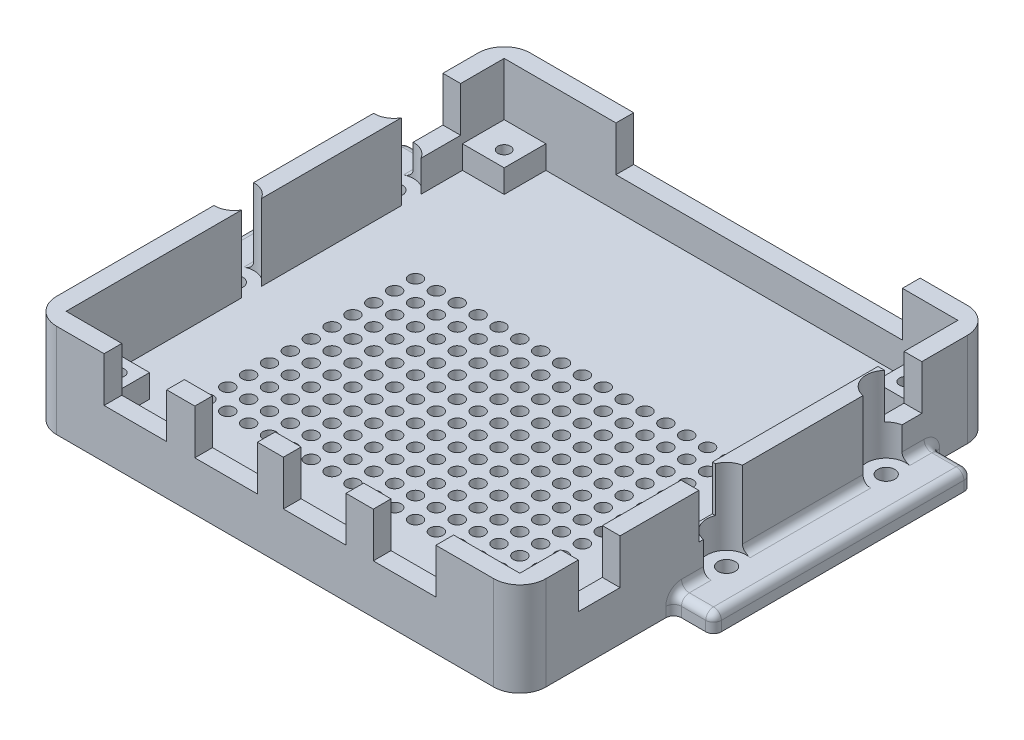
SolidWorks part; units mm, degrees
material "ABS"
ref_plane "Front Plane" through (0, 0, 0) normal (0, 0, 1) x (1, 0, 0)
ref_plane "Top Plane" through (0, 0, 0) normal (0, 1, 0) x (1, 0, 0)
ref_plane "Right Plane" through (0, 0, 0) normal (1, 0, 0) x (0, 0, -1)
sketch "Sketch1" plane through (0, 60.3244, 0) normal (0, 1, 0) x (1, 0, 0)
  line L0 (-17.8987, -37.9421) -> (-17.8987, -46.2606) construction
  line L1 (-17.8987, -46.2606) -> (-17.8987, -58.5796) construction
  line L2 (-24.7567, -58.5796) -> (-11.0407, -58.5796) construction
  line L3 (-17.8987, -58.5796) -> (-17.8987, -139.5421) construction
  line L4 (-17.8987, -139.5421) -> (-6.8751, -139.5421) construction
  line L5 (-17.8987, -139.5421) -> (87.5113, -139.5421) construction
  line L6 (-6.8751, -139.5421) -> (8.3649, -139.5421) construction
  line L7 (8.3649, -139.5421) -> (15.2229, -139.5421) construction
  line L8 (15.2229, -139.5421) -> (30.4629, -139.5421) construction
  line L9 (30.4629, -139.5421) -> (36.7875, -139.5421) construction
  line L10 (36.7875, -139.5421) -> (52.0275, -139.5421) construction
  line L11 (52.0275, -139.5421) -> (58.6823, -139.5421) construction
  line L12 (58.6823, -139.5421) -> (73.9223, -139.5421) construction
  line L13 (73.9223, -139.5421) -> (87.5113, -139.5421) construction
  line L14 (87.5113, -139.5421) -> (87.5113, -132.1507) construction
  line L15 (87.5113, -102.8137) -> (87.5113, -139.5421) construction
  line L16 (87.5113, -132.1507) -> (87.5113, -121.9907) construction
  line L17 (87.5113, -121.9907) -> (87.5113, -102.8137) construction
  line L18 (87.5113, -102.8137) -> (87.5113, -95.1937) construction
  line L19 (87.5113, -95.1937) -> (87.5113, -54.8585) construction
  line L20 (87.5113, -37.9421) -> (87.5113, -95.1937) construction
  line L21 (87.5113, -54.8585) -> (87.5113, -48.5085) construction
  line L22 (87.5113, -48.5085) -> (87.5113, -37.9421) construction
  line L23 (87.5113, -37.9421) -> (76.5401, -37.9421) construction
  line L24 (-17.8987, -37.9421) -> (87.5113, -37.9421) construction
  line L25 (76.5401, -37.9421) -> (53.8801, -37.9421) construction
  line L26 (53.8801, -37.9421) -> (52.3339, -37.9421) construction
  line L27 (52.3339, -37.9421) -> (29.6739, -37.9421) construction
  line L28 (29.6739, -37.9421) -> (29.4485, -37.9421) construction
  line L29 (29.4485, -37.9421) -> (6.7885, -37.9421) construction
  line L30 (6.7885, -37.9421) -> (-17.8987, -37.9421) construction
  line L31 (-24.7567, -58.712) -> (-24.7567, -146.4001)
  line L32 (-20.4387, -142.0821) -> (-6.8751, -142.0821)
  line L33 (6.7885, -35.4021) -> (-20.4387, -35.4021)
  line L34 (-24.7567, -31.0841) -> (-24.7567, -46.0066)
  line L35 (90.0513, -48.5085) -> (90.0513, -35.4021)
  line L36 (90.0513, -35.4021) -> (76.5401, -35.4021)
  line L37 (90.0513, -95.1937) -> (90.0513, -54.8585)
  line L38 (90.0513, -121.9907) -> (90.0513, -102.8137)
  line L39 (73.9223, -142.0821) -> (90.0513, -142.0821)
  line L40 (90.0513, -142.0821) -> (90.0513, -132.1507)
  line L41 (52.0275, -142.0821) -> (58.6823, -142.0821)
  line L42 (30.4629, -142.0821) -> (36.7875, -142.0821)
  line L43 (8.3649, -142.0821) -> (15.2229, -142.0821)
  line L44 (6.7885, -31.0841) -> (-24.7567, -31.0841)
  line L45 (-20.4387, -46.0066) -> (-20.4387, -35.4021)
  line L46 (-20.4387, -142.0821) -> (-20.4387, -58.712)
  line L47 (-24.7567, -146.4001) -> (-6.8751, -146.4001)
  line L48 (8.3649, -146.4001) -> (15.2229, -146.4001)
  line L49 (30.4629, -146.4001) -> (36.7875, -146.4001)
  line L50 (52.0275, -146.4001) -> (58.6823, -146.4001)
  line L51 (73.9223, -146.4001) -> (94.3693, -146.4001)
  line L52 (94.3693, -146.4001) -> (94.3693, -132.1507)
  line L53 (94.3693, -121.9907) -> (94.3693, -102.8137)
  line L54 (94.3693, -95.1937) -> (94.3693, -54.8585)
  line L55 (94.3693, -48.5085) -> (94.3693, -31.0841)
  line L56 (94.3693, -31.0841) -> (76.5401, -31.0841)
  line L57 (-24.7567, -58.712) -> (-20.4387, -58.712)
  line L58 (-24.7567, -46.0066) -> (-20.4387, -46.0066)
  line L60 (-24.7567, -58.5796) -> (-17.8987, -58.5796) construction
  line L62 (6.7885, -31.0841) -> (6.7885, -35.4021)
  line L63 (76.5401, -35.4021) -> (76.5401, -31.0841)
  line L64 (90.0513, -48.5085) -> (94.3693, -48.5085)
  line L65 (90.0513, -54.8585) -> (94.3693, -54.8585)
  line L66 (90.0513, -95.1937) -> (94.3693, -95.1937)
  line L67 (90.0513, -102.8137) -> (94.3693, -102.8137)
  line L68 (90.0513, -121.9907) -> (94.3693, -121.9907)
  line L69 (90.0513, -132.1507) -> (94.3693, -132.1507)
  line L70 (73.9223, -142.0821) -> (73.9223, -146.4001)
  line L71 (58.6823, -146.4001) -> (58.6823, -142.0821)
  line L72 (52.0275, -142.0821) -> (52.0275, -146.4001)
  line L73 (36.7875, -146.4001) -> (36.7875, -142.0821)
  line L74 (30.4629, -142.0821) -> (30.4629, -146.4001)
  line L75 (15.2229, -142.0821) -> (15.2229, -146.4001)
  line L76 (8.3649, -142.0821) -> (8.3649, -146.4001)
  line L77 (-6.8751, -142.0821) -> (-6.8751, -146.4001)
  line L78 (-24.7567, -58.5796) -> (-24.7567, -146.4001) construction
  line L79 (-20.4387, -58.5796) -> (-20.4387, -142.0821) construction
  line L80 (-24.7567, -31.0841) -> (-24.7567, -46.2606) construction
  line L81 (-20.4387, -35.4021) -> (-20.4387, -46.2606) construction
  dimension "D1" = 0.1324
extrude "Boss-Extrude2" add sketch "Sketch1" along normal up to surface (10.922 mm away)
sketch "Sketch2" plane through (0, 60.3244, 0) normal (0, -1, 0) x (1, 0, 0)
  line L0 (87.5113, 37.9421) -> (87.5113, 139.5421) construction
  line L1 (-24.7567, 146.4001) -> (94.3693, 146.4001)
  line L2 (-24.7567, 146.4001) -> (-24.7567, 31.0841)
  line L3 (-24.7567, 31.0841) -> (94.3693, 31.0841)
  line L4 (94.3693, 146.4001) -> (94.3693, 31.0841)
  line L5 (-10.2787, 45.5621) -> (-17.8987, 45.5621)
  line L6 (-10.2787, 45.5621) -> (-10.2787, 37.9421)
  line L7 (-10.2787, 37.9421) -> (-17.8987, 37.9421)
  line L8 (-17.8987, 45.5621) -> (-17.8987, 37.9421)
  line L9 (-10.2787, 45.5621) -> (-17.8987, 37.9421) construction
  line L10 (-10.2787, 37.9421) -> (-17.8987, 45.5621) construction
  line L11 (-10.2787, 131.9221) -> (-17.8987, 131.9221)
  line L12 (-10.2787, 131.9221) -> (-10.2787, 139.5421)
  line L13 (-10.2787, 139.5421) -> (-17.8987, 139.5421)
  line L14 (-17.8987, 131.9221) -> (-17.8987, 139.5421)
  line L15 (-10.2787, 131.9221) -> (-17.8987, 139.5421) construction
  line L16 (-10.2787, 139.5421) -> (-17.8987, 131.9221) construction
  line L17 (79.8913, 131.9221) -> (87.5113, 131.9221)
  line L18 (79.8913, 131.9221) -> (79.8913, 139.5421)
  line L19 (79.8913, 139.5421) -> (87.5113, 139.5421)
  line L20 (87.5113, 131.9221) -> (87.5113, 139.5421)
  line L21 (79.8913, 131.9221) -> (87.5113, 139.5421) construction
  line L22 (79.8913, 139.5421) -> (87.5113, 131.9221) construction
  line L23 (79.8913, 45.5621) -> (87.5113, 45.5621)
  line L24 (79.8913, 45.5621) -> (79.8913, 37.9421)
  line L25 (79.8913, 37.9421) -> (87.5113, 37.9421)
  line L26 (87.5113, 45.5621) -> (87.5113, 37.9421)
  line L27 (79.8913, 45.5621) -> (87.5113, 37.9421) construction
  line L28 (79.8913, 37.9421) -> (87.5113, 45.5621) construction
  line L29 (-17.8987, 37.9421) -> (87.5113, 37.9421) construction
  line L30 (-24.7567, 46.0066) -> (-20.4387, 46.0066)
  line L31 (-10.2787, 131.9221) -> (-24.7567, 131.9221)
  line L32 (-10.2787, 131.9221) -> (-10.2787, 146.4001)
  line L33 (-10.2787, 146.4001) -> (-24.7567, 146.4001)
  line L34 (-24.7567, 131.9221) -> (-24.7567, 146.4001)
  line L35 (79.8913, 131.9221) -> (94.3693, 131.9221)
  line L36 (79.8913, 131.9221) -> (79.8913, 146.4001)
  line L37 (79.8913, 146.4001) -> (94.3693, 146.4001)
  line L38 (94.3693, 131.9221) -> (94.3693, 146.4001)
  line L39 (-10.2787, 45.5621) -> (-24.7567, 45.5621)
  line L40 (-10.2787, 45.5621) -> (-10.2787, 31.0841)
  line L41 (-10.2787, 31.0841) -> (-24.7567, 31.0841)
  line L42 (-24.7567, 45.5621) -> (-24.7567, 31.0841)
  line L43 (79.8913, 45.5621) -> (94.3693, 45.5621)
  line L44 (79.8913, 45.5621) -> (79.8913, 31.0841)
  line L45 (79.8913, 31.0841) -> (94.3693, 31.0841)
  line L46 (94.3693, 45.5621) -> (94.3693, 31.0841)
  line L47 (-20.4387, 46.0066) -> (-20.4387, 45.5621)
  line L48 (-20.4387, 46.0066) -> (-20.4387, 35.4021) construction
  line L49 (-20.4387, 45.5621) -> (-24.7567, 45.5621)
  line L51 (-20.4387, 142.0821) -> (90.0513, 142.0821)
  line L52 (-20.4387, 142.0821) -> (-20.4387, 35.4021)
  line L53 (-20.4387, 35.4021) -> (90.0513, 35.4021)
  line L54 (90.0513, 142.0821) -> (90.0513, 35.4021)
  circle A0 centre (83.7013, 135.7321) radius 1.524
  circle A1 centre (-14.0887, 135.7321) radius 1.524
  circle A2 centre (-14.0887, 41.7521) radius 1.524
  circle A3 centre (83.7013, 41.7521) radius 1.524
  point P6 (-14.0887, 41.7521)
  point P13 (-14.0887, 135.7321)
  point P20 (83.7013, 135.7321)
  point P27 (83.7013, 41.7521)
  line M1 (-20.4387, 58.712) -> (-20.4387, 142.0821)
  line M2 (-20.4387, 142.0821) -> (-6.8751, 142.0821)
  line M3 (-6.8751, 142.0821) -> (-6.8751, 146.4001)
  line M4 (-6.8751, 146.4001) -> (-24.7567, 146.4001)
  line M5 (-24.7567, 146.4001) -> (-24.7567, 58.712)
  line M6 (-24.7567, 58.712) -> (-20.4387, 58.712)
extrude "Boss-Extrude4" add sketch "Sketch2" along normal blind 7.62 contours L43 L54 L53 L44 L3 L4 | L35 L54 L43 L4 | L51 L54 L35 L4 L1 L36 | L53 L40 L3 L44 | L53 L52 L39 L2 L3 L40 | L52 L2 L30 M6 | L47 L30 L2 L39 | L31 L2 M1 M6 | L32 L1 L31 M2 M5 M1 | L32 M2 M3 M4 | L51 L36 L1 M3 region at (-17.5177, 60.3244, 146.1953) region at (-8.5769, 60.3244, 144.2411) region at (-22.5977, 60.3244, 95.317) region at (36.5081, 60.3244, 144.2411) region at (-22.5977, 60.3244, 52.3593) region at (87.1303, 60.3244, 146.1953) region at (-22.5977, 60.3244, 45.7843) region at (-22.5977, 60.3244, 45.3573) region at (92.2103, 60.3244, 88.7421) region at (94.1646, 60.3244, 38.3231) region at (34.8063, 60.3244, 33.2431)
sketch "Sketch5" plane through (0, 58.3244, 0) normal (0, -1, 0) x (1, 0, 0)
  line L0 (-20.4387, 142.0821) -> (90.0513, 142.0821) construction
  line L1 (-10.2787, 131.9221) -> (-17.8987, 131.9221)
  line L2 (-10.2787, 131.9221) -> (-10.2787, 139.5421)
  line L3 (-10.2787, 139.5421) -> (-17.8987, 139.5421)
  line L4 (-17.8987, 131.9221) -> (-17.8987, 139.5421)
  line L5 (-10.2787, 131.9221) -> (-17.8987, 139.5421) construction
  line L6 (-10.2787, 139.5421) -> (-17.8987, 131.9221) construction
  line L7 (79.8913, 131.9221) -> (87.5113, 131.9221)
  line L8 (79.8913, 131.9221) -> (79.8913, 139.5421)
  line L9 (79.8913, 139.5421) -> (87.5113, 139.5421)
  line L10 (87.5113, 131.9221) -> (87.5113, 139.5421)
  line L11 (79.8913, 131.9221) -> (87.5113, 139.5421) construction
  line L12 (79.8913, 139.5421) -> (87.5113, 131.9221) construction
  line L13 (79.8913, 45.5621) -> (87.5113, 45.5621)
  line L14 (79.8913, 45.5621) -> (79.8913, 37.9421)
  line L15 (79.8913, 37.9421) -> (87.5113, 37.9421)
  line L16 (87.5113, 45.5621) -> (87.5113, 37.9421)
  line L17 (79.8913, 45.5621) -> (87.5113, 37.9421) construction
  line L18 (79.8913, 37.9421) -> (87.5113, 45.5621) construction
  line L19 (-10.2787, 45.5621) -> (-17.8987, 45.5621)
  line L20 (-10.2787, 45.5621) -> (-10.2787, 37.9421)
  line L21 (-10.2787, 37.9421) -> (-17.8987, 37.9421)
  line L22 (-17.8987, 45.5621) -> (-17.8987, 37.9421)
  line L23 (-10.2787, 45.5621) -> (-17.8987, 37.9421) construction
  line L24 (-10.2787, 37.9421) -> (-17.8987, 45.5621) construction
  line L25 (-10.2787, 131.9221) -> (-20.4387, 131.9221)
  line L26 (-10.2787, 131.9221) -> (-10.2787, 142.0821)
  line L27 (-10.2787, 142.0821) -> (-20.4387, 142.0821)
  line L28 (-20.4387, 131.9221) -> (-20.4387, 142.0821)
  line L29 (-20.4387, 142.0821) -> (-20.4387, 35.4021) construction
  line L30 (90.0513, 142.0821) -> (90.0513, 35.4021) construction
  line L31 (79.8913, 131.9221) -> (90.0513, 131.9221)
  line L32 (79.8913, 131.9221) -> (79.8913, 142.0821)
  line L33 (79.8913, 142.0821) -> (90.0513, 142.0821)
  line L34 (90.0513, 131.9221) -> (90.0513, 142.0821)
  line L35 (79.8913, 45.5621) -> (90.0513, 45.5621)
  line L36 (79.8913, 45.5621) -> (79.8913, 35.4021)
  line L37 (79.8913, 35.4021) -> (90.0513, 35.4021)
  line L38 (90.0513, 45.5621) -> (90.0513, 35.4021)
  line L39 (-10.2787, 45.5621) -> (-20.4387, 45.5621)
  line L40 (-10.2787, 45.5621) -> (-10.2787, 35.4021)
  line L41 (-10.2787, 35.4021) -> (-20.4387, 35.4021)
  line L42 (-20.4387, 45.5621) -> (-20.4387, 35.4021)
  line L43 (-20.4387, 35.4021) -> (90.0513, 35.4021) construction
  point P0 (-14.0887, 135.7321)
  point P7 (83.7013, 135.7321)
  point P14 (83.7013, 41.7521)
  point P21 (-14.0887, 41.7521)
  circle M1 centre (-14.0887, 135.7321) radius 1.524
  circle M2 centre (83.7013, 135.7321) radius 1.524
  circle M3 centre (83.7013, 41.7521) radius 1.524
  circle M4 centre (-14.0887, 41.7521) radius 1.524
  line M5 (-17.8987, 139.5421) -> (-17.8987, 37.9421)
  line M6 (-17.8987, 37.9421) -> (87.5113, 37.9421)
  line M7 (87.5113, 37.9421) -> (87.5113, 139.5421)
  line M8 (87.5113, 139.5421) -> (-17.8987, 139.5421)
extrude "Boss-Extrude6" add sketch "Sketch5" along normal up to surface (5.62 mm away) contours L28 L25 L26 L27 M5 M8 | L1 L2 M8 M5 M1 | L8 L7 M7 M8 M2 | L31 L34 L33 L32 M8 M7 | L13 L14 M6 M7 M3 | L38 L35 L36 L37 M7 M6 | L20 L19 M5 M6 M4 | L39 L42 L41 L40 M6 M5 region at (-14.0887, 58.3244, 132.0298) region at (-19.1687, 58.3244, 132.0657) region at (-14.0887, 58.3244, 45.4543) region at (-18.0424, 58.3244, 41.7521) region at (83.7013, 58.3244, 139.4343) region at (80.035, 58.3244, 140.8121) region at (79.9991, 58.3244, 41.7521) region at (83.7013, 58.3244, 37.7984) up to face at (34.8063, 52.7044, 88.7421)
sketch "Sketch6" plane through (0, 52.7044, 0) normal (0, -1, 0) x (-1, 0, 0)
  line L1 (24.7567, -146.4001) -> (-94.3693, -146.4001)
  line L2 (24.7567, -146.4001) -> (24.7567, -31.0841)
  line L3 (24.7567, -31.0841) -> (-94.3693, -31.0841)
  line L4 (-94.3693, -146.4001) -> (-94.3693, -31.0841)
  circle A0 centre (14.0887, -135.7321) radius 1.524
  circle A1 centre (-83.7013, -135.7321) radius 1.524
  circle A2 centre (-83.7013, -41.7521) radius 1.524
  circle A3 centre (14.0887, -41.7521) radius 1.524
extrude "Boss-Extrude7" add sketch "Sketch6" along normal blind 4.318
sketch "Sketch7" plane through (0, 48.3864, 0) normal (0, -1, 0) x (1, 0, 0)
  line L0 (94.3693, 31.0841) -> (94.3693, 146.4001) construction
  line L1 (72.9063, 74.1371) -> (-3.2937, 74.1371) construction
  line L2 (72.9063, 74.1371) -> (72.9063, 124.8101) construction
  line L3 (72.9063, 124.8101) -> (-3.2937, 124.8101) construction
  line L4 (-3.2937, 74.1371) -> (-3.2937, 124.8101) construction
  line L5 (-24.7567, 146.4001) -> (-24.7567, 31.0841) construction
  line L6 (94.3693, 146.4001) -> (-24.7567, 146.4001) construction
  line L7 (-24.7567, 31.0841) -> (94.3693, 31.0841) construction
  line L8 (-3.2937, 99.4736) -> (72.9063, 99.4736) construction
  line L9 (34.8063, 74.1371) -> (34.8063, 124.8101) construction
  line L10 (72.9063, 74.1371) -> (67.8263, 74.1371) construction
  circle A0 centre (72.9063, 74.1371) radius 1.5875
  circle A1 centre (67.8263, 74.1371) radius 1.5875
  circle A2 centre (62.7463, 74.1371) radius 1.5875
  circle A3 centre (57.6663, 74.1371) radius 1.5875
  circle A4 centre (52.5863, 74.1371) radius 1.5875
  circle A5 centre (47.5063, 74.1371) radius 1.5875
  circle A6 centre (42.4263, 74.1371) radius 1.5875
  circle A7 centre (37.3463, 74.1371) radius 1.5875
  circle A8 centre (32.2663, 74.1371) radius 1.5875
  circle A9 centre (27.1863, 74.1371) radius 1.5875
  circle A10 centre (22.1063, 74.1371) radius 1.5875
  circle A11 centre (17.0263, 74.1371) radius 1.5875
  circle A12 centre (11.9463, 74.1371) radius 1.5875
  circle A13 centre (6.8663, 74.1371) radius 1.5875
  circle A14 centre (1.7863, 74.1371) radius 1.5875
  circle A15 centre (-3.2937, 74.1371) radius 1.5875
  circle A16 centre (72.9063, 79.2171) radius 1.5875
  circle A17 centre (67.8263, 79.2171) radius 1.5875
  circle A18 centre (62.7463, 79.2171) radius 1.5875
  circle A19 centre (57.6663, 79.2171) radius 1.5875
  circle A20 centre (52.5863, 79.2171) radius 1.5875
  circle A21 centre (47.5063, 79.2171) radius 1.5875
  circle A22 centre (42.4263, 79.2171) radius 1.5875
  circle A23 centre (37.3463, 79.2171) radius 1.5875
  circle A24 centre (32.2663, 79.2171) radius 1.5875
  circle A25 centre (27.1863, 79.2171) radius 1.5875
  circle A26 centre (22.1063, 79.2171) radius 1.5875
  circle A27 centre (17.0263, 79.2171) radius 1.5875
  circle A28 centre (11.9463, 79.2171) radius 1.5875
  circle A29 centre (6.8663, 79.2171) radius 1.5875
  circle A30 centre (1.7863, 79.2171) radius 1.5875
  circle A31 centre (-3.2937, 79.2171) radius 1.5875
  circle A32 centre (72.9063, 84.2971) radius 1.5875
  circle A33 centre (67.8263, 84.2971) radius 1.5875
  circle A34 centre (62.7463, 84.2971) radius 1.5875
  circle A35 centre (57.6663, 84.2971) radius 1.5875
  circle A36 centre (52.5863, 84.2971) radius 1.5875
  circle A37 centre (47.5063, 84.2971) radius 1.5875
  circle A38 centre (42.4263, 84.2971) radius 1.5875
  circle A39 centre (37.3463, 84.2971) radius 1.5875
  circle A40 centre (32.2663, 84.2971) radius 1.5875
  circle A41 centre (27.1863, 84.2971) radius 1.5875
  circle A42 centre (22.1063, 84.2971) radius 1.5875
  circle A43 centre (17.0263, 84.2971) radius 1.5875
  circle A44 centre (11.9463, 84.2971) radius 1.5875
  circle A45 centre (6.8663, 84.2971) radius 1.5875
  circle A46 centre (1.7863, 84.2971) radius 1.5875
  circle A47 centre (-3.2937, 84.2971) radius 1.5875
  circle A48 centre (72.9063, 89.3771) radius 1.5875
  circle A49 centre (67.8263, 89.3771) radius 1.5875
  circle A50 centre (62.7463, 89.3771) radius 1.5875
  circle A51 centre (57.6663, 89.3771) radius 1.5875
  circle A52 centre (52.5863, 89.3771) radius 1.5875
  circle A53 centre (47.5063, 89.3771) radius 1.5875
  circle A54 centre (42.4263, 89.3771) radius 1.5875
  circle A55 centre (37.3463, 89.3771) radius 1.5875
  circle A56 centre (32.2663, 89.3771) radius 1.5875
  circle A57 centre (27.1863, 89.3771) radius 1.5875
  circle A58 centre (22.1063, 89.3771) radius 1.5875
  circle A59 centre (17.0263, 89.3771) radius 1.5875
  circle A60 centre (11.9463, 89.3771) radius 1.5875
  circle A61 centre (6.8663, 89.3771) radius 1.5875
  circle A62 centre (1.7863, 89.3771) radius 1.5875
  circle A63 centre (-3.2937, 89.3771) radius 1.5875
  circle A64 centre (72.9063, 94.4571) radius 1.5875
  circle A65 centre (67.8263, 94.4571) radius 1.5875
  circle A66 centre (62.7463, 94.4571) radius 1.5875
  circle A67 centre (57.6663, 94.4571) radius 1.5875
  circle A68 centre (52.5863, 94.4571) radius 1.5875
  circle A69 centre (47.5063, 94.4571) radius 1.5875
  circle A70 centre (42.4263, 94.4571) radius 1.5875
  circle A71 centre (37.3463, 94.4571) radius 1.5875
  circle A72 centre (32.2663, 94.4571) radius 1.5875
  circle A73 centre (27.1863, 94.4571) radius 1.5875
  circle A74 centre (22.1063, 94.4571) radius 1.5875
  circle A75 centre (17.0263, 94.4571) radius 1.5875
  circle A76 centre (11.9463, 94.4571) radius 1.5875
  circle A77 centre (6.8663, 94.4571) radius 1.5875
  circle A78 centre (1.7863, 94.4571) radius 1.5875
  circle A79 centre (-3.2937, 94.4571) radius 1.5875
  circle A80 centre (72.9063, 99.5371) radius 1.5875
  circle A81 centre (67.8263, 99.5371) radius 1.5875
  circle A82 centre (62.7463, 99.5371) radius 1.5875
  circle A83 centre (57.6663, 99.5371) radius 1.5875
  circle A84 centre (52.5863, 99.5371) radius 1.5875
  circle A85 centre (47.5063, 99.5371) radius 1.5875
  circle A86 centre (42.4263, 99.5371) radius 1.5875
  circle A87 centre (37.3463, 99.5371) radius 1.5875
  circle A88 centre (32.2663, 99.5371) radius 1.5875
  circle A89 centre (27.1863, 99.5371) radius 1.5875
  circle A90 centre (22.1063, 99.5371) radius 1.5875
  circle A91 centre (17.0263, 99.5371) radius 1.5875
  circle A92 centre (11.9463, 99.5371) radius 1.5875
  circle A93 centre (6.8663, 99.5371) radius 1.5875
  circle A94 centre (1.7863, 99.5371) radius 1.5875
  circle A95 centre (-3.2937, 99.5371) radius 1.5875
  circle A96 centre (72.9063, 104.6171) radius 1.5875
  circle A97 centre (67.8263, 104.6171) radius 1.5875
  circle A98 centre (62.7463, 104.6171) radius 1.5875
  circle A99 centre (57.6663, 104.6171) radius 1.5875
  circle A100 centre (52.5863, 104.6171) radius 1.5875
  circle A101 centre (47.5063, 104.6171) radius 1.5875
  circle A102 centre (42.4263, 104.6171) radius 1.5875
  circle A103 centre (37.3463, 104.6171) radius 1.5875
  circle A104 centre (32.2663, 104.6171) radius 1.5875
  circle A105 centre (27.1863, 104.6171) radius 1.5875
  circle A106 centre (22.1063, 104.6171) radius 1.5875
  circle A107 centre (17.0263, 104.6171) radius 1.5875
  circle A108 centre (11.9463, 104.6171) radius 1.5875
  circle A109 centre (6.8663, 104.6171) radius 1.5875
  circle A110 centre (1.7863, 104.6171) radius 1.5875
  circle A111 centre (-3.2937, 104.6171) radius 1.5875
  circle A112 centre (72.9063, 109.6971) radius 1.5875
  circle A113 centre (67.8263, 109.6971) radius 1.5875
  circle A114 centre (62.7463, 109.6971) radius 1.5875
  circle A115 centre (57.6663, 109.6971) radius 1.5875
  circle A116 centre (52.5863, 109.6971) radius 1.5875
  circle A117 centre (47.5063, 109.6971) radius 1.5875
  circle A118 centre (42.4263, 109.6971) radius 1.5875
  circle A119 centre (37.3463, 109.6971) radius 1.5875
  circle A120 centre (32.2663, 109.6971) radius 1.5875
  circle A121 centre (27.1863, 109.6971) radius 1.5875
  circle A122 centre (22.1063, 109.6971) radius 1.5875
  circle A123 centre (17.0263, 109.6971) radius 1.5875
  circle A124 centre (11.9463, 109.6971) radius 1.5875
  circle A125 centre (6.8663, 109.6971) radius 1.5875
  circle A126 centre (1.7863, 109.6971) radius 1.5875
  circle A127 centre (-3.2937, 109.6971) radius 1.5875
  circle A128 centre (72.9063, 114.7771) radius 1.5875
  circle A129 centre (67.8263, 114.7771) radius 1.5875
  circle A130 centre (62.7463, 114.7771) radius 1.5875
  circle A131 centre (57.6663, 114.7771) radius 1.5875
  circle A132 centre (52.5863, 114.7771) radius 1.5875
  circle A133 centre (47.5063, 114.7771) radius 1.5875
  circle A134 centre (42.4263, 114.7771) radius 1.5875
  circle A135 centre (37.3463, 114.7771) radius 1.5875
  circle A136 centre (32.2663, 114.7771) radius 1.5875
  circle A137 centre (27.1863, 114.7771) radius 1.5875
  circle A138 centre (22.1063, 114.7771) radius 1.5875
  circle A139 centre (17.0263, 114.7771) radius 1.5875
  circle A140 centre (11.9463, 114.7771) radius 1.5875
  circle A141 centre (6.8663, 114.7771) radius 1.5875
  circle A142 centre (1.7863, 114.7771) radius 1.5875
  circle A143 centre (-3.2937, 114.7771) radius 1.5875
  circle A144 centre (72.9063, 119.8571) radius 1.5875
  circle A145 centre (67.8263, 119.8571) radius 1.5875
  circle A146 centre (62.7463, 119.8571) radius 1.5875
  circle A147 centre (57.6663, 119.8571) radius 1.5875
  circle A148 centre (52.5863, 119.8571) radius 1.5875
  circle A149 centre (47.5063, 119.8571) radius 1.5875
  circle A150 centre (42.4263, 119.8571) radius 1.5875
  circle A151 centre (37.3463, 119.8571) radius 1.5875
  circle A152 centre (32.2663, 119.8571) radius 1.5875
  circle A153 centre (27.1863, 119.8571) radius 1.5875
  circle A154 centre (22.1063, 119.8571) radius 1.5875
  circle A155 centre (17.0263, 119.8571) radius 1.5875
  circle A156 centre (11.9463, 119.8571) radius 1.5875
  circle A157 centre (6.8663, 119.8571) radius 1.5875
  circle A158 centre (1.7863, 119.8571) radius 1.5875
  circle A159 centre (-3.2937, 119.8571) radius 1.5875
  circle A160 centre (72.9063, 124.9371) radius 1.5875
  circle A161 centre (67.8263, 124.9371) radius 1.5875
  circle A162 centre (62.7463, 124.9371) radius 1.5875
  circle A163 centre (57.6663, 124.9371) radius 1.5875
  circle A164 centre (52.5863, 124.9371) radius 1.5875
  circle A165 centre (47.5063, 124.9371) radius 1.5875
  circle A166 centre (42.4263, 124.9371) radius 1.5875
  circle A167 centre (37.3463, 124.9371) radius 1.5875
  circle A168 centre (32.2663, 124.9371) radius 1.5875
  circle A169 centre (27.1863, 124.9371) radius 1.5875
  circle A170 centre (22.1063, 124.9371) radius 1.5875
  circle A171 centre (17.0263, 124.9371) radius 1.5875
  circle A172 centre (11.9463, 124.9371) radius 1.5875
  circle A173 centre (6.8663, 124.9371) radius 1.5875
  circle A174 centre (1.7863, 124.9371) radius 1.5875
  circle A175 centre (-3.2937, 124.9371) radius 1.5875
  dimension "D5" = 50.673
  dimension "D7" = 5.08
  dimension "D6" = 16
  dimension "D1" = 21.463
  dimension "D2" = 21.463
  dimension "D3" = 21.59
  dimension "D4" = 43.053
  dimension "D8" = 11
extrude "Cut-Extrude1" cut sketch "Sketch7" against normal up to surface (4.318 mm away) up to face at (34.8063, 52.7044, 88.7421)
fillet "Fillet1" radius 6.35 4 edges at (-24.7567, 59.8164, 31.0841) (94.3693, 59.8164, 31.0841) (94.3693, 59.8164, 146.4001) (-24.7567, 59.8164, 146.4001)
sketch "Sketch8" plane through (0, 48.3864, 0) normal (0, -1, 0) x (1, 0, 0)
  line L0 (-18.4067, 31.0841) -> (88.0193, 31.0841) construction
  line L1 (-34.4722, 46.0701) -> (104.0848, 46.0701)
  line L2 (-34.4722, 46.0701) -> (-34.4722, 108.9351)
  line L3 (-34.4722, 108.9351) -> (104.0848, 108.9351)
  line L4 (104.0848, 46.0701) -> (104.0848, 108.9351)
  line L5 (-24.7567, 140.0501) -> (-24.7567, 37.4341) construction
  line L6 (94.3693, 37.4341) -> (94.3693, 140.0501) construction
  line L7 (-34.4722, 46.0701) -> (-24.7567, 46.0701)
  line L8 (-34.4722, 46.0701) -> (-34.4722, 108.9351)
  line L9 (-34.4722, 108.9351) -> (-24.7567, 108.9351)
  line L10 (-24.7567, 46.0701) -> (-24.7567, 108.9351)
  line L11 (104.0848, 46.0701) -> (94.3693, 46.0701)
  line L12 (104.0848, 46.0701) -> (104.0848, 108.9351)
  line L13 (104.0848, 108.9351) -> (94.3693, 108.9351)
  line L14 (94.3693, 46.0701) -> (94.3693, 108.9351)
  circle A1 centre (-24.6297, 58.0716) radius 2.0955
  circle A2 centre (-24.6297, 96.9336) radius 2.0955
  circle A3 centre (95.2583, 58.0716) radius 2.0955
  circle A4 centre (95.2583, 96.9336) radius 2.0955
  dimension "D5" = 12.0015
  dimension "D7" = 9.8425
  dimension "D9" = 12.0015
  dimension "D10" = 12.0015
  dimension "D1" = 62.865
  dimension "D2" = 138.557
  dimension "D3" = 14.986
  dimension "D4" = 9.7155
  dimension "D6" = 12.0015
  dimension "D8" = 8.8265
extrude "Boss-Extrude8" add sketch "Sketch8" against normal blind 4.318 contours A2 L10 L3 L2 L1 A1 | A4 L14 A3 L1 L4 L3 region at (-29.7002, 48.3864, 77.5026) region at (99.353, 48.3864, 77.5026)
sketch "Sketch9" plane through (0, 48.3864, 0) normal (0, -1, 0) x (1, 0, 0)
  circle A0 centre (-24.6297, 58.0716) radius 2.0955
  circle A1 centre (95.2583, 96.9336) radius 2.0955
  circle A2 centre (-24.6297, 96.9336) radius 2.0955
  circle A3 centre (95.2583, 58.0716) radius 2.0955
extrude "Cut-Extrude2" cut sketch "Sketch9" against normal up to surface (22.86 mm away) up to face at (-17.6947, 71.2464, 119.3933)
sketch "Sketch10" plane through (0, 52.7044, 0) normal (0, 1, 0) x (1, 0, 0)
  circle A0 centre (95.2583, -96.9336) radius 4.826
  circle A1 centre (95.2583, -58.0716) radius 4.826
  circle A2 centre (-24.6297, -96.9336) radius 4.826
  circle A3 centre (-24.6297, -58.0716) radius 4.826
extrude "Cut-Extrude3" cut sketch "Sketch10" along normal up to surface (18.542 mm away) up to face at (-19.3539, 71.2464, 109.0147)
fillet "Fillet14" radius 1.905 10 edges at (104.0848, 50.5454, 46.0701) (99.2271, 52.7044, 46.0701) (104.0848, 52.7044, 77.5026) (104.0848, 50.5454, 108.9351) (99.2271, 52.7044, 108.9351) (-34.4722, 50.5454, 108.9351) (-29.6144, 52.7044, 108.9351) (-34.4722, 52.7044, 77.5026) (-34.4722, 50.5454, 46.0701) (-29.6144, 52.7044, 46.0701)
fillet "Fillet15" radius 1.905 14 edges at (-24.7567, 49.5929, 108.9351) (-24.7567, 52.1465, 108.3771) (-24.7567, 52.7044, 104.394) (-24.7567, 52.7044, 77.5026) (-24.7567, 52.7044, 50.6111) (-24.7567, 52.1465, 46.628) (-24.7567, 49.5929, 46.0701) (94.3693, 52.7044, 77.5026) (94.3693, 52.7044, 104.3535) (94.3693, 52.1465, 108.3771) (94.3693, 49.5929, 108.9351) (94.3693, 52.1465, 46.628) (94.3693, 52.7044, 50.6516) (94.3693, 49.5929, 46.0701)
